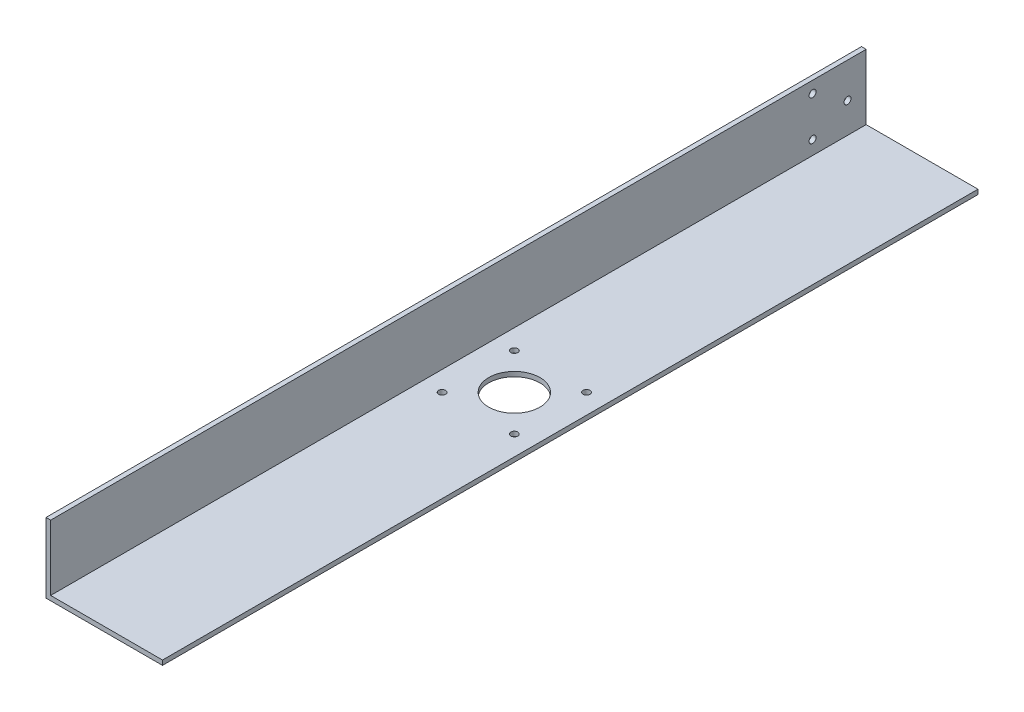
SolidWorks part; units mm, degrees
ref_plane "Front Plane" through (0, 0, 0) normal (0, 0, 1) x (1, 0, 0)
ref_plane "Top Plane" through (0, 0, 0) normal (0, 1, 0) x (1, 0, 0)
ref_plane "Right Plane" through (0, 0, 0) normal (1, 0, 0) x (0, 0, -1)
sketch "Sketch1" plane through (0, 0, 0) normal (0, 0, 1) x (1, 0, 0)
  line L0 (0, 0) -> (0, 30)
  line L1 (0, 30) -> (2, 30)
  line L2 (2, 30) -> (2, 2)
  line L3 (2, 2) -> (50, 2)
  line L4 (50, 2) -> (50, 0)
  line L5 (50, 0) -> (0, 0)
extrude "Boss-Extrude1" add sketch "Sketch1" along normal up to surface (350 mm away)
sketch "Sketch7" plane through (0, 2, 0) normal (0, 1, 0) x (1, 0, 0)
  circle A0 centre (26, -175) radius 11
  point P7 (2, -350)
extrude "Cut-Extrude1" cut sketch "Sketch7" against normal through all from surface starting at face at (26, 2, 175)
sketch "Sketch8" plane through (0, 2, 0) normal (0, 1, 0) x (1, 0, 0)
  circle A0 centre (41.5, -190.5) radius 1.5
  circle A1 centre (41.5, -159.5) radius 1.5
  circle A2 centre (10.5, -190.5) radius 1.5
  circle A3 centre (10.5, -159.5) radius 1.5
extrude "Cut-Extrude2" cut sketch "Sketch8" against normal through all
hole_wizard "Ø3.0 (3) Diameter Hole1" positions "Sketch9" profile "Sketch10" hole size "Ø3.0" standard "ISO"
sketch "Sketch9" plane through (0, 182.32, 128.862) normal (-1, 0, 0) x (0, 0, -1)
  point P0 (105.862, 174.32)
  point P2 (105.862, 157.32)
  point P4 (120.862, 167.32)
sketch "Sketch10" plane through (0, 8, 23) normal (0, 1, 0) x (0, 0, 1)
  line L0 (0, 0) -> (0, 1.999)
  line L1 (0, 1.999) -> (1.5, 1.999)
  line L2 (1.5, 1.999) -> (1.5, 0)
  line L3 (1.5, 0) -> (0, 0)
  line L4 (0, -6.35) -> (0, 107.95) construction
  dimension "Thru Hole Dia." = 3
  dimension "Thru Hole Depth" = 1.999
